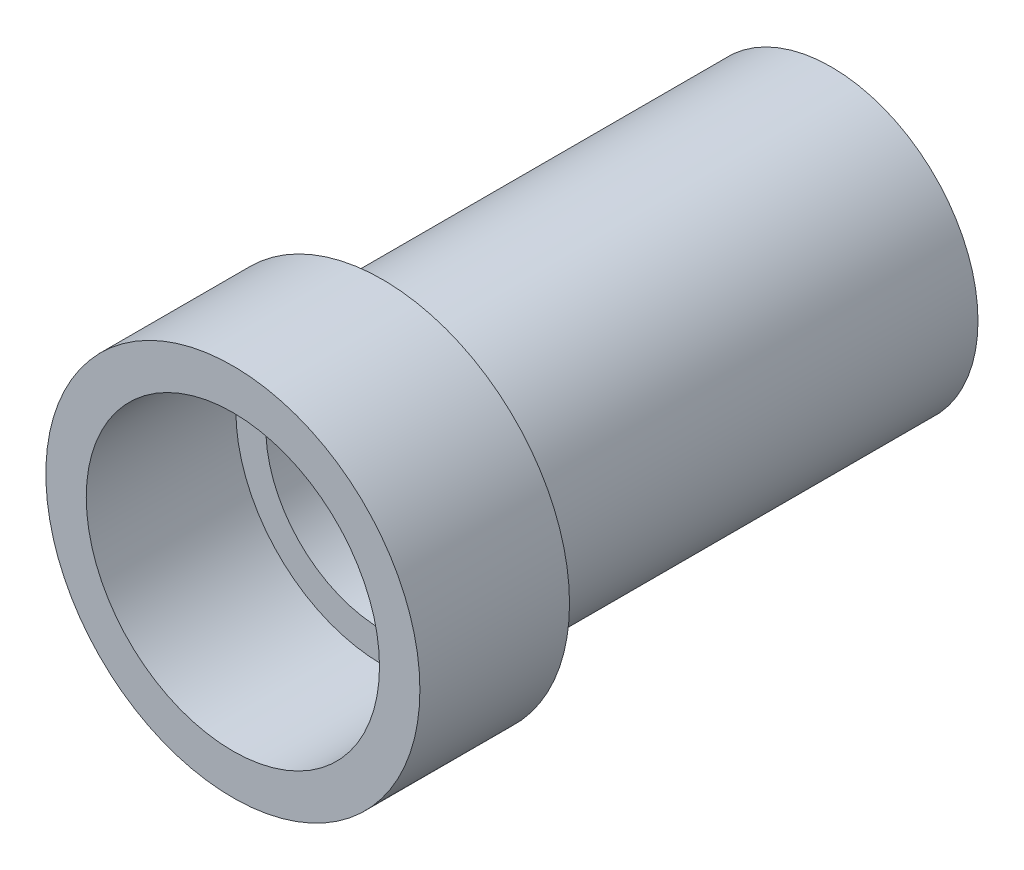
SolidWorks part; units mm, degrees
ref_plane "Front Plane" through (0, 0, 0) normal (0, 0, 1) x (1, 0, 0)
ref_plane "Top Plane" through (0, 0, 0) normal (0, 1, 0) x (1, 0, 0)
ref_plane "Right Plane" through (0, 0, 0) normal (1, 0, 0) x (0, 0, -1)
sketch "Sketch1" plane through (0, 0, 0) normal (0, 0, 1) x (1, 0, 0)
  circle A0 centre (0, 142.24) radius 12.446 construction
  circle A1 centre (0, 142.24) radius 12.446
  circle A2 centre (0, 142.24) radius 15.875
  dimension "D1" = 31.75
extrude "Extrude-Thin1" add sketch "Sketch1" against normal blind 38.1 thin contours A1 thin type one direction reverse wall 2.54
extrude "Extrude1" add sketch "Sketch1<3>" along normal blind 12.7 separate body
sketch "Sketch1<3>" plane through (0, 0, 0) normal (0, 0, 1) x (1, 0, 0) same geometry as "Sketch1"
